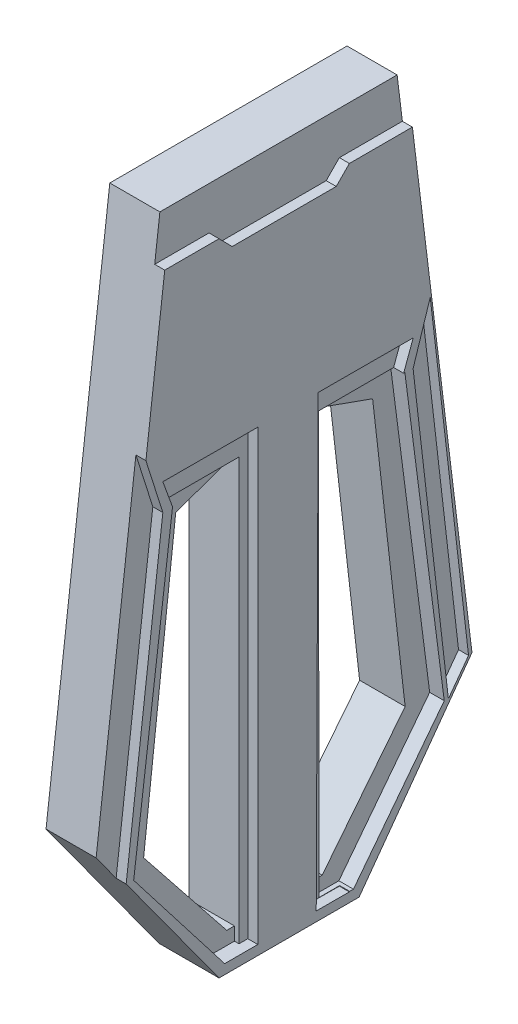
SolidWorks part; units mm, degrees
ref_plane "Front Plane" through (0, 0, 0) normal (0, 0, 1) x (1, 0, 0)
ref_plane "Top Plane" through (0, 0, 0) normal (0, 1, 0) x (1, 0, 0)
ref_plane "Right Plane" through (0, 0, 0) normal (1, 0, 0) x (0, 0, -1)
sketch "Sketch1" plane through (0, 0, 0) normal (1, 0, 0) x (0, 0, -1)
  line L0 (-267.5417, -157.2454) -> (307.7917, -157.2454) construction
  line L1 (0.0004, 0) -> (30.7498, 0)
  line L2 (30.7498, 0) -> (55.5435, 34.1255)
  line L3 (55.5435, 34.1255) -> (41.3066, 150)
  line L4 (41.3066, 150) -> (-10.7931, 150)
  line L5 (-10.7931, 150) -> (-24.7936, 34.126)
  line L6 (-24.7936, 34.126) -> (0.0004, 0)
  line L7 (15.7806, -32.7217) -> (15.7806, 0) construction
  dimension "D1" = 54
  dimension "D6" = 54
extrude "Boss-Extrude1" add sketch "Sketch1" along normal blind 13.2 contours L1 L2 L3 L4 L5 L6
sketch "Sketch2" plane through (13.2, 0, 0) normal (1, 0, 0) x (0, 0, -1)
  line L0 (-16.0591, 106.4163) -> (-12.3445, 94.7038)
  line L1 (-10.7931, 150) -> (-24.7936, 34.126) construction
  line L2 (-12.3445, 94.7038) -> (-20.3953, 28.0722)
  line L3 (-24.7936, 34.126) -> (0.0004, 0) construction
  line L4 (-20.3953, 28.0722) -> (-24.7936, 34.126)
  line L5 (-24.7936, 34.126) -> (-16.0591, 106.4163)
  line L6 (14.5984, -146.9171) -> (15.2568, 150)
  line L7 (-12.3445, 100.5506) -> (8.5157, 100.5044)
  line L8 (41.3066, 150) -> (-10.7931, 150) construction
  line L13 (-12.3445, 100.5506) -> (-10.2107, 94.7038)
  line L14 (-10.2107, 94.7038) -> (-18.7486, 27.9478)
  line L15 (-18.7486, 27.9478) -> (1.2335, 2.1156)
  line L16 (1.2335, 2.1156) -> (8.5157, 2.1156)
  line L17 (50.3678, 27.9153) -> (54.793, 33.9495)
  line L18 (42.6126, 94.5819) -> (50.3678, 27.9153)
  line L19 (46.3791, 106.2779) -> (42.6126, 94.5819)
  line L20 (8.5157, 100.5044) -> (8.5157, 2.1156)
  line L21 (54.793, 33.9495) -> (46.3791, 106.2779)
  line L22 (48.7206, 27.7982) -> (28.6242, 2.0548)
  line L23 (40.4788, 94.5914) -> (48.7206, 27.7982)
  line L24 (42.6385, 100.4287) -> (40.4788, 94.5914)
  line L25 (42.6385, 100.4287) -> (21.7784, 100.475)
  line L26 (21.7784, 100.475) -> (21.342, 2.0871)
  line L27 (28.6242, 2.0548) -> (21.342, 2.0871)
  line L34 (-10.7931, 150) -> (-11.9292, 140.5972)
  line L35 (-11.9292, 140.5972) -> (0, 140.5972)
  line L36 (0, 140.5972) -> (2.8852, 137.6728)
  line L37 (41.3066, 150) -> (42.461, 140.6047)
  line L38 (55.5435, 34.1255) -> (41.3066, 150) construction
  line L39 (42.461, 140.6047) -> (28.6242, 140.6047)
  line L40 (28.6242, 140.6047) -> (25.7389, 137.6728)
  line L41 (25.7389, 137.6728) -> (2.8852, 137.6728)
  line L42 (-10.7931, 150) -> (41.3066, 150)
  point P12 (14.9276, 1.5414)
  line M6 (-24.7936, 34.126) -> (0.0004, 0)
  line M8 (30.7498, 0) -> (55.5435, 34.1255)
  line M9 (55.5435, 34.1255) -> (41.3066, 150)
  line M10 (41.3066, 150) -> (-10.7931, 150)
  line M11 (-10.7931, 150) -> (-24.7936, 34.126)
extrude "Cut-Extrude1" cut sketch "Sketch2" against normal blind 2.2 contours L27 L22 L23 L24 L25 L26 | L19 L18 M9 M8 | L2 L0 M11 M6 | L20 L7 L13 L14 L15 L16 | L41 L6 L35 L36 M10 M11 | L41 L40 L39 L6 M9 M10 region at (13.2, 65.8899, 18.4257) region at (13.2, 144.4218, -2.8251) region at (13.2, 144.5224, -27.667) region at (13.2, 52.4883, 2.588) region at (13.2, 65.7413, -48.5659) region at (13.2, 52.4102, -32.6689)
sketch "Sketch5" plane through (13.2, 0, 0) normal (1, 0, 0) x (0, 0, -1)
  line L1 (6.5824, 94.7038) -> (-10.2107, 94.7038)
  line L8 (15.2568, 150) -> (15.3751, 0) construction
  line L9 (41.3066, 150) -> (-10.7931, 150) construction
  line L10 (0.0004, 0) -> (30.7498, 0) construction
  line L12 (6.5824, 94.7038) -> (6.5824, 2.1156)
  line L13 (1.2335, 2.1156) -> (8.5157, 2.1156) construction
  line L14 (6.5824, 2.1156) -> (1.2335, 2.1156)
  line L15 (1.2335, 2.1156) -> (-18.7486, 27.9478)
  line L16 (-18.7486, 27.9478) -> (-10.2107, 94.7038)
  line L19 (49.4547, 28.0016) -> (40.8115, 94.744)
  line L20 (29.5134, 2.1379) -> (49.4547, 28.0016)
  line L21 (24.1645, 2.1294) -> (29.5134, 2.1379)
  line L22 (24.0184, 94.7175) -> (24.1645, 2.1294)
  line L23 (24.0184, 94.7175) -> (40.8115, 94.744)
extrude "Cut-Extrude5" cut sketch "Sketch5" against normal blind 3.2
sketch "Sketch8" plane through (10, 0, 0) normal (1, 0, 0) x (0, 0, -1)
  line L0 (6.5824, 94.7038) -> (-6.3142, 90.0651)
  line L1 (-6.3142, 90.0651) -> (-13.365, 27.9478)
  line L2 (-13.365, 27.9478) -> (4.8882, 5.0202)
  line L3 (4.8882, 5.0202) -> (6.5824, 5.0202)
  line L4 (6.5824, 2.1156) -> (6.5824, 94.7038) construction
  line L5 (6.5824, 5.0202) -> (6.5824, 94.7038)
  line L6 (15.2568, 150) -> (15.3751, 0) construction
  line L7 (41.3066, 150) -> (-10.7931, 150) construction
  line L8 (0.0004, 0) -> (30.7498, 0) construction
  line L9 (25.8541, 5.0368) -> (24.1599, 5.0341)
  line L10 (44.0711, 27.9931) -> (25.8541, 5.0368)
  line L11 (36.9223, 90.0992) -> (44.0711, 27.9931)
  line L12 (24.0184, 94.7175) -> (36.9223, 90.0992)
  line L13 (24.1599, 5.0341) -> (24.0184, 94.7175)
extrude "Cut-Extrude7" cut sketch "Sketch8" against normal blind 47.2
